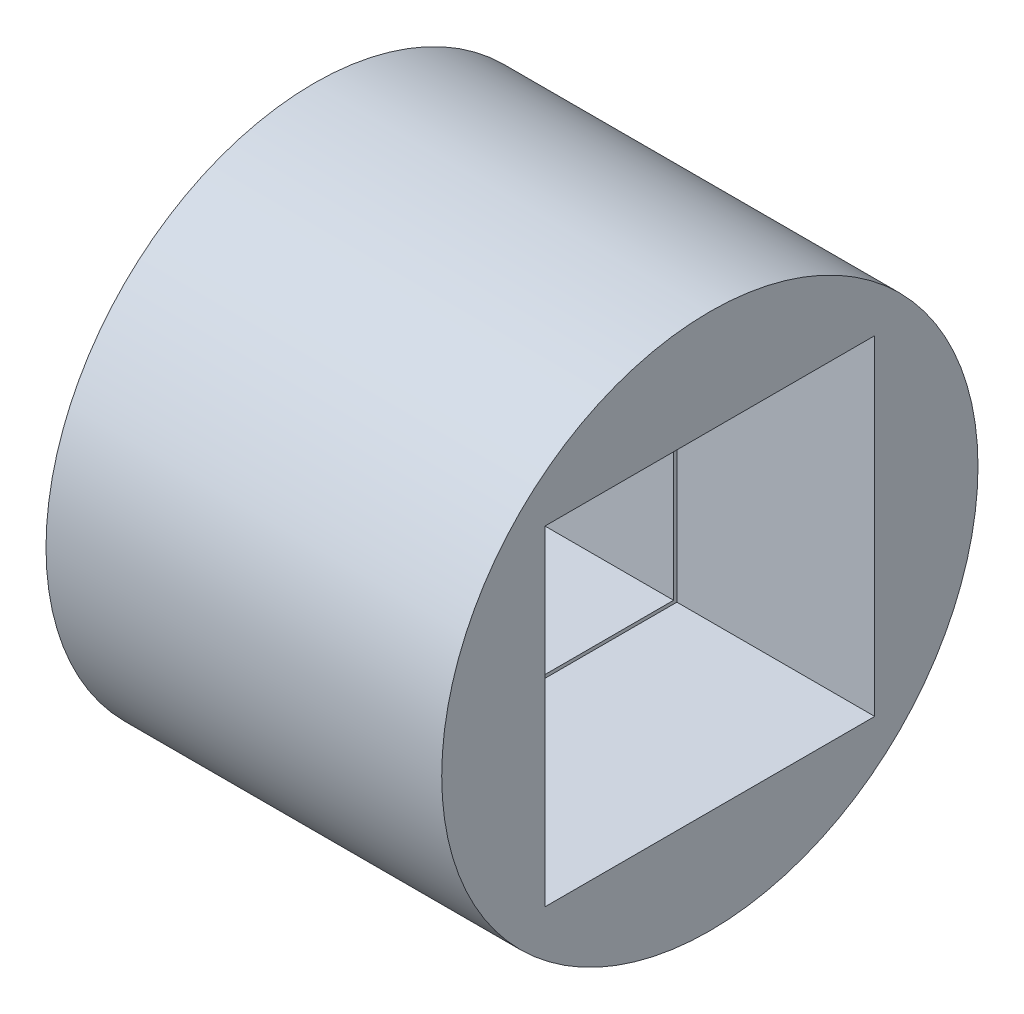
SolidWorks part; units mm, degrees
ref_plane "前视基准面" through (0, 0, 0) normal (0, 0, 1) x (1, 0, 0)
ref_plane "上视基准面" through (0, 0, 0) normal (0, 1, 0) x (1, 0, 0)
ref_plane "右视基准面" through (0, 0, 0) normal (1, 0, 0) x (0, 0, -1)
sketch "草图1" plane through (0, 0, 0) normal (1, 0, 0) x (0, 0, -1)
  line L1 (-2.5, -2.5) -> (2.5, -2.5)
  line L2 (-2.5, -2.5) -> (-2.5, 2.5)
  line L3 (-2.5, 2.5) -> (2.5, 2.5)
  line L4 (2.5, -2.5) -> (2.5, 2.5)
  line L5 (-2.5, -2.5) -> (2.5, 2.5) construction
  line L6 (-2.5, 2.5) -> (2.5, -2.5) construction
  circle A0 centre (0, 0) radius 4.0658
  dimension "D1" = 5
  dimension "D2" = 5
extrude "凸台-拉伸1" add sketch "草图1" along normal blind 3
sketch "草图2" plane through (0, 0, 0) normal (-1, 0, 0) x (0, 0, 1)
  line L12 (-2.45, -2.45) -> (2.45, -2.45)
  line L13 (-2.45, 2.45) -> (-2.45, -2.45)
  line L14 (2.45, 2.45) -> (-2.45, 2.45)
  line L15 (2.45, -2.45) -> (2.45, 2.45)
  line L16 (-2.45, -2.45) -> (2.45, -2.45)
  line L17 (-2.45, 2.45) -> (-2.45, -2.45)
  line L18 (2.45, 2.45) -> (-2.45, 2.45)
  line L19 (2.45, -2.45) -> (2.45, 2.45)
  circle A1 centre (0, 0) radius 4.0658
  circle A2 centre (0, 0) radius 4.0658
  dimension "D1" = 0
  dimension "D2" = 0.05
extrude "凸台-拉伸2" add sketch "草图2" along normal blind 3
